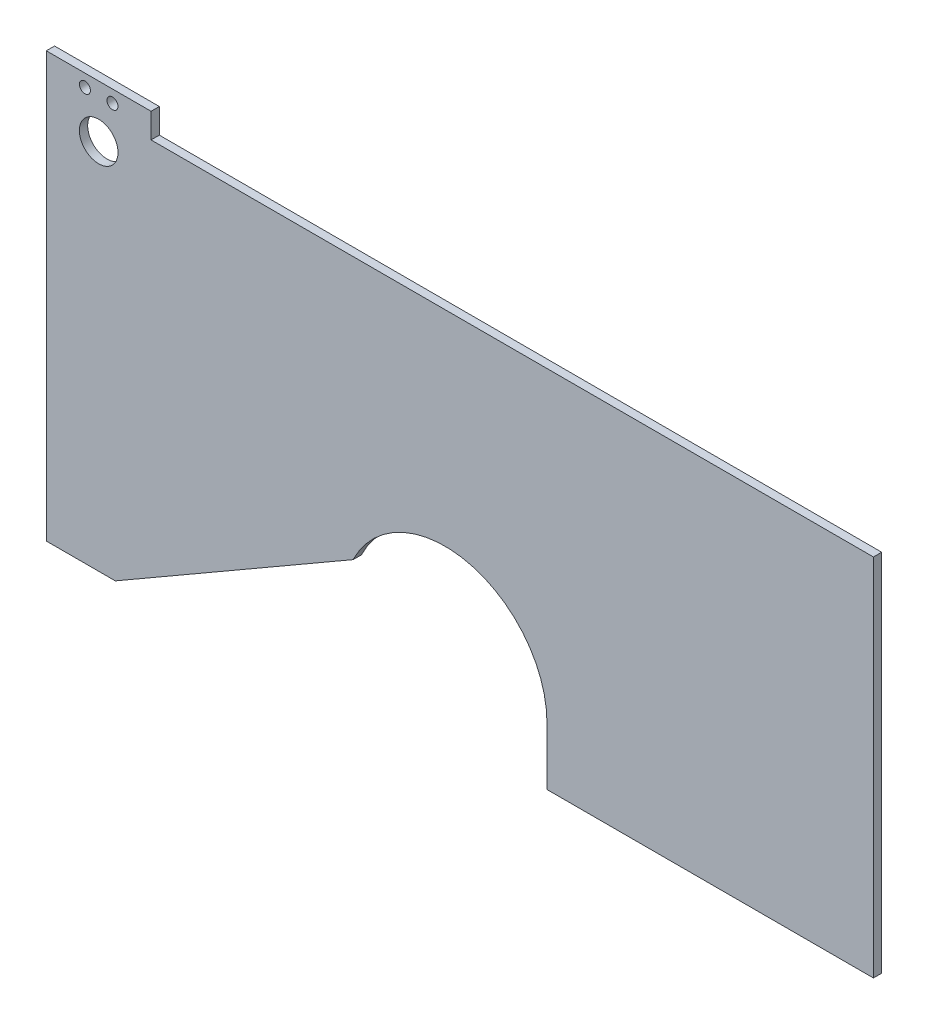
SolidWorks part; units mm, degrees
ref_plane "Front Plane" through (0, 0, 0) normal (0, 0, 1) x (1, 0, 0)
ref_plane "Top Plane" through (0, 0, 0) normal (0, 1, 0) x (1, 0, 0)
ref_plane "Right Plane" through (0, 0, 0) normal (1, 0, 0) x (0, 0, -1)
sketch "Sketch2" plane through (0, 0, 0) normal (0, 0, 1) x (1, 0, 0)
  line L0 (25.0304, 0) -> (111.2865, 49.8)
  line L1 (0, 0) -> (25.0304, 0)
  line L2 (0, 0) -> (0, 154)
  line L4 (300, 0) -> (300, 145)
  line L5 (181.6, 33.7) -> (181.6, 0)
  line L6 (181.6, 0) -> (300, 0)
  line L7 (19, 135) -> (19, 164.3674) construction
  line L11 (38, 145) -> (300, 145)
  line L12 (0, 154) -> (19, 154)
  line L13 (19, 154) -> (38, 154)
  line L14 (38, 154) -> (38, 145)
  line L15 (19, 135) -> (50019, 135) construction
  line L20 (19, 135) -> (19, -49865) construction
  circle A0 centre (19, 135) radius 7
  arc A1 (181.6, 33.7) -> (111.2865, 49.8) centre (144.6, 33.7) ccw
  circle A2 centre (14, 149.5) radius 2
  circle A3 centre (24, 149.5) radius 2
  point P8 (0, 0)
  point P14 (315, 145)
  point P16 (0, 0)
  point P19 (19, 154)
  dimension "D3" = 135
  dimension "D4" = 19
  dimension "D5" = 14
  dimension "D6" = 74
  dimension "D7" = 155.4
  dimension "D8" = 33.7
  dimension "D13" = 4
  dimension "D14" = 5
  dimension "D15" = 14.5
  dimension "D1" = 300
  dimension "D2" = 154
  dimension "D9" = 30
  dimension "D10" = 99.6
  dimension "D11" = 19
  dimension "D12" = 145
  dimension "D16" = 9
extrude "Boss-Extrude2" add sketch "Sketch2" along normal blind 3
sketch "Sketch3" plane through (0, 0, 3) normal (0, 0, 1) x (1, 0, 0)
  line L0 (300, 0) -> (300, 145) construction
  line L1 (181.6, 0) -> (300, 0)
  line L2 (181.6, 0) -> (181.6, 12.75)
  line L3 (181.6, 12.75) -> (300, 12.75)
  line L4 (300, 0) -> (300, 12.75)
  dimension "D1" = 12.75
extrude "Cut-Extrude1" cut sketch "Sketch3" against normal through all
sketch "Sketch4" plane through (0, 0, 3) normal (0, 0, 1) x (1, 0, 0)
  line L0 (19, 135) -> (19, -49865) construction
  line L1 (19, 135) -> (-49981, 135) construction
